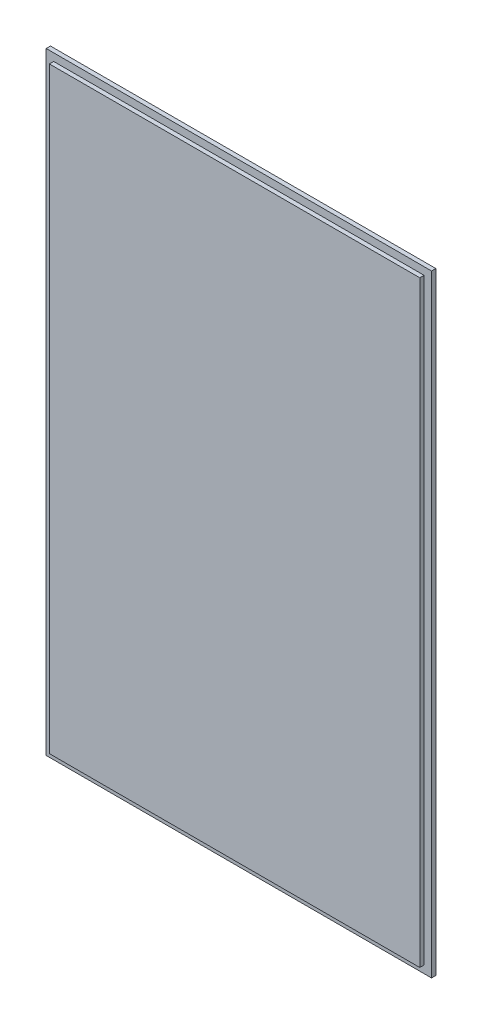
SolidWorks part; units mm, degrees
ref_plane "Přední rovina" through (0, 0, 0) normal (0, 0, 1) x (1, 0, 0)
ref_plane "Horní rovina" through (0, 0, 0) normal (0, 1, 0) x (1, 0, 0)
ref_plane "Pravá rovina" through (0, 0, 0) normal (1, 0, 0) x (0, 0, -1)
sketch "Skica1" plane through (0, 0, 0) normal (0, 0, 1) x (1, 0, 0)
  line L1 (0, 0) -> (72, 0)
  line L2 (0, 0) -> (0, 114.4)
  line L3 (0, 114.4) -> (72, 114.4)
  line L4 (72, 0) -> (72, 114.4)
  dimension "D1" = 114.4
  dimension "D2" = 72
extrude "Přidat vysunutím1" add sketch "Skica1" along normal blind 0.8
sketch "Skica2" plane through (0, 0, 0.8) normal (0, 0, 1) x (1, 0, 0)
  line L1 (1.4, 113) -> (70.6, 113)
  line L6 (1.4, 113) -> (1.4, 1.4)
  line L14 (0, 114.4) -> (0, 0) construction
  line L16 (1.4, 1.4) -> (70.6, 1.4)
  line L17 (70.6, 1.4) -> (70.6, 113)
  line L18 (72, 0) -> (72, 114.4) construction
  line L21 (72, 114.4) -> (0, 114.4) construction
  line L22 (0, 0) -> (72, 0) construction
  dimension "D1" = 1.4
  dimension "D2" = 1.4
  dimension "D3" = 1.4
  dimension "D4" = 1.4
extrude "Přidat vysunutím2" add sketch "Skica2" along normal blind 0.8
